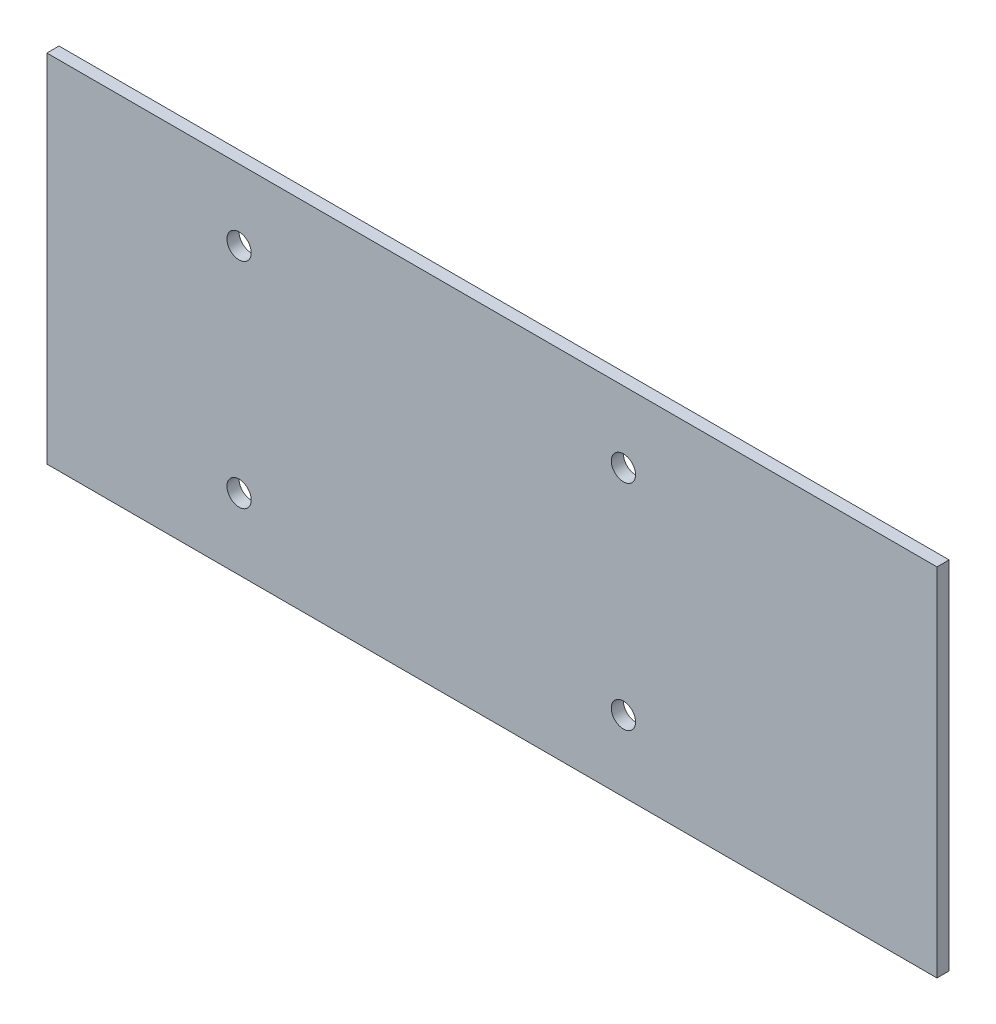
SolidWorks part; units mm, degrees
material "Plain Carbon Steel"
ref_plane "Front Plane" through (0, 0, 0) normal (0, 0, 1) x (1, 0, 0)
ref_plane "Top Plane" through (0, 0, 0) normal (0, 1, 0) x (1, 0, 0)
ref_plane "Right Plane" through (0, 0, 0) normal (1, 0, 0) x (0, 0, -1)
sketch "Sketch1" plane through (0, 0, 0) normal (0, 0, 1) x (1, 0, 0)
  line L0 (55, 0) -> (-55, 0) construction
  line L1 (-345, 52.92) -> (-155, 52.92) construction
  line L2 (-345, 52.92) -> (-345, -52.92) construction
  line L3 (-345, -52.92) -> (-155, -52.92) construction
  line L4 (-155, 52.92) -> (-155, -52.92) construction
  line L5 (0, -55) -> (0, 55) construction
  line L7 (0, -88) -> (-395, -88)
  line L8 (0, -88) -> (0, 88)
  line L9 (0, 88) -> (-395, 88)
  line L10 (-395, -88) -> (-395, 88)
  circle A0 centre (-345, 52.92) radius 6
  circle A1 centre (-155, 52.92) radius 6
  circle A2 centre (-155, -52.92) radius 6
  circle A3 centre (-345, -52.92) radius 6
  point P4 (-345, 0)
  point P14 (0, 0)
  dimension "D3" = 12
  dimension "D1" = 105.84
  dimension "D2" = 190
  dimension "D4" = 395
  dimension "D5" = 176
  dimension "D6" = 50
  dimension "D7" = 88
extrude "Boss-Extrude1" add sketch "Sketch1" along normal blind 6
sketch "Sketch2" plane through (-395, 0, 0) normal (-1, 0, 0) x (0, 0, 1)
  line L0 (6, 88) -> (6, -88) construction
  line L1 (0, 88) -> (6, 88)
  line L2 (0, 88) -> (0, -88)
  line L3 (0, -88) -> (6, -88)
  line L4 (6, 88) -> (6, -88)
extrude "Boss-Extrude2" add sketch "Sketch2" along normal blind 45
